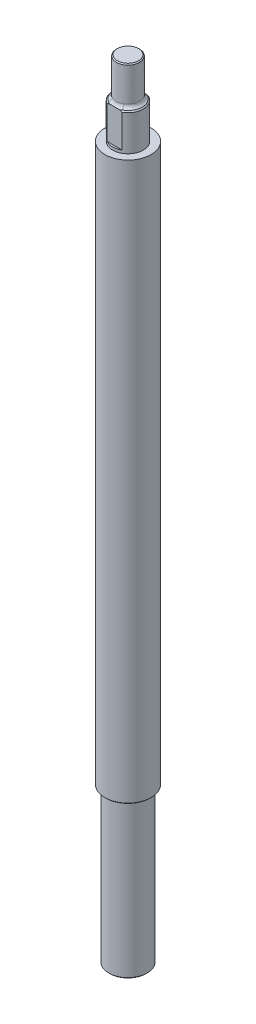
SolidWorks part; units mm, degrees
material "1.0037 (S235JR)"
ref_plane "Front Plane" through (0, 0, 0) normal (0, 0, 1) x (1, 0, 0)
ref_plane "Top Plane" through (0, 0, 0) normal (0, 1, 0) x (1, 0, 0)
ref_plane "Right Plane" through (0, 0, 0) normal (1, 0, 0) x (0, 0, -1)
sketch "Sketch3" plane through (0, 0, 0) normal (0, 1, 0) x (1, 0, 0)
  circle A0 centre (0, 0) radius 6
  dimension "D1" = 12
extrude "Boss-Extrude1" add sketch "Sketch3" along normal blind 145 contours A0
sketch "Sketch4" plane through (0, 145, 0) normal (0, 1, 0) x (1, 0, 0)
  circle A0 centre (0, 0) radius 4
  dimension "D1" = 8
extrude "Boss-Extrude2" add sketch "Sketch4" along normal blind 9.5
sketch "Sketch6" plane through (0, 0, 0) normal (0, -1, 0) x (1, 0, 0)
  circle A0 centre (0, 0) radius 5
  dimension "D1" = 10
extrude "Boss-Extrude3" add sketch "Sketch6" along normal blind 40 contours A0
sketch "Sketch7" plane through (0, 154.5, 0) normal (0, 1, 0) x (1, 0, 0)
  circle A0 centre (0, 0) radius 3
  dimension "D1" = 6
extrude "Boss-Extrude4" add sketch "Sketch7" along normal blind 10
cosmetic thread "Rosca cosmética1" parameters "D1"=8.884, "D2"=4.891
sketch "Sketch9" plane through (0, -40, 0) normal (0, -1, 0) x (-1, 0, 0)
  point P0 (0, 0)
  point P1 (0, 0)
ref_plane "Plano2" through (0, 0, 3) normal (0, 0, 1) x (1, 0, 0)
ref_plane "Plano3" through (0, 0, 3.5) normal (0, 0, 1) x (1, 0, 0)
ref_plane "Plano5" through (0, 0, -4.25) normal (0, 0, 1) x (1, 0, 0)
sketch "Croquis9" plane through (0, 0, 3.5) normal (0, 0, 1) x (1, 0, 0)
  line L0 (4, 154.5) -> (-4, 154.5) construction
  line L1 (-3, 145.75) -> (3, 145.75)
  line L2 (-3, 145.75) -> (-3, 154.5)
  line L4 (3, 145.75) -> (3, 154.5)
  line L5 (4, 145) -> (4, 154.5) construction
  line L10 (6, 145) -> (-6, 145) construction
  line L13 (-3, 154.5) -> (3, 154.5)
  line L14 (-4, 154.5) -> (-4, 145) construction
  dimension "D1" = 0.75
  dimension "D2" = 1
  dimension "D3" = 1
extrude "Cortar-Extruir1" cut sketch "Croquis9" along normal blind 1.25
pattern_circular "MatrizC1" count 2 over 360 about axis through (0, 154.5, 0) along (0, -1, 0) of "Cortar-Extruir1"
fillet "Redondeo2" radius 1 1 edges at (0, 154.5, 3)
chamfer "Chaflán1" distance 0.25 angle 45 3 edges at (0, -40, -5) (0, 0, 6) (0, 164.5, 3)
cosmetic thread "Rosca cosmética3" parameters "D1"=23, "D2"=8.344
chamfer "Chaflán2" distance 0.25 angle 45 2 edges at (-4, 154.5, 0) (4, 154.5, 0)
